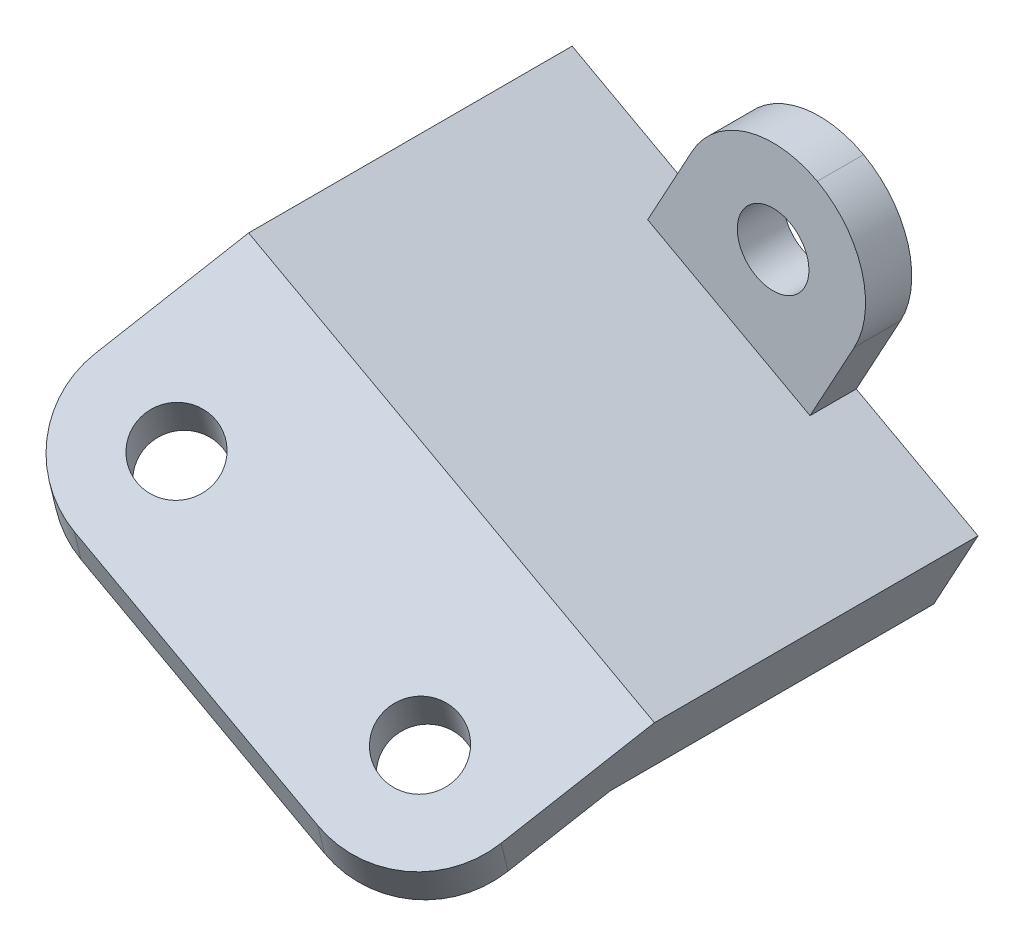
SolidWorks part; units mm, degrees
ref_plane "Front Plane" through (0, 0, 0) normal (0, 0, 1) x (1, 0, 0)
ref_plane "Top Plane" through (0, 0, 0) normal (0, 1, 0) x (1, 0, 0)
ref_plane "Right Plane" through (0, 0, 0) normal (1, 0, 0) x (0, 0, -1)
sketch "Sketch1" plane through (0, 0, 0) normal (0, 0, 1) x (1, 0, 0)
  line L0 (70, 136) -> (70, 0) construction
  line L2 (70, 114.8055) -> (60.4274, 97.2452)
  line L3 (60.4274, 97.2452) -> (53.4032, 101.0743)
  line L4 (53.4032, 101.0743) -> (62.9759, 118.6346)
  line L5 (62.9759, 118.6346) -> (70, 114.8055)
  dimension "D1" = 20
  dimension "D2" = 8
extrude "Boss-Extrude1" add sketch "Sketch1" along normal blind 2
fillet "Fillet1" radius 4 4 edges at (60.4274, 97.2452, 1) (53.4032, 101.0743, 1) (70, 114.8055, 1) (62.9759, 118.6346, 1)
sketch "Sketch2" plane through (0, 0, 2) normal (0, 0, 1) x (1, 0, 0)
  circle A0 centre (64.5734, 113.208) radius 1.55
  circle A1 centre (58.8298, 102.6718) radius 1.55
  dimension "D1" = 3.1
  dimension "D2" = 3.1
extrude "Cut-Extrude1" cut sketch "Sketch2" against normal up to next
sketch "Sketch3" plane through (0, 0, 2) normal (0, 0, 1) x (1, 0, 0)
  line L0 (66.1709, 107.7814) -> (59.1468, 111.6105)
  line L1 (62.3419, 100.7573) -> (68.0855, 111.2935) construction
  line L2 (61.0613, 115.1225) -> (55.3178, 104.5864) construction
  line L3 (64.2564, 104.2694) -> (57.2323, 108.0984)
  line L4 (65.2137, 106.0254) -> (58.1896, 109.8545) construction
  line L5 (66.1709, 107.7814) -> (71.439, 104.9096)
  line L6 (64.2564, 104.2694) -> (69.5245, 101.3976)
  line L7 (69.5245, 101.3976) -> (71.439, 104.9096)
  line L8 (59.1468, 111.6105) -> (53.8787, 114.4823)
  line L9 (53.8787, 114.4823) -> (51.9642, 110.9702)
  line L10 (51.9642, 110.9702) -> (57.2323, 108.0984)
  dimension "D3" = 6
  dimension "D1" = 2
  dimension "D2" = 2
  dimension "D4" = 6
extrude "Boss-Extrude2" add sketch "Sketch3" along normal blind 12 and the other way up to surface (2 mm away) other way up to face at (57.2798, 102.6718, 0)
sketch "Sketch4" plane through (-6.5751, 3.5843, 0) normal (-0.878, 0.4786, 0) x (0, 0, 1)
  line L0 (14, 122.3053) -> (20.9282, 118.3053)
  line L1 (14, 126.3053) -> (22.6603, 121.3053)
  line L2 (22.6603, 121.3053) -> (20.9282, 118.3053)
  line L3 (20.9282, 118.3053) -> (24.0467, 118.1828)
  line L4 (0, 122.3053) -> (14, 122.3053) construction
  line M4 (14, 122.3053) -> (14, 126.3053)
  dimension "D1" = 8
  dimension "D2" = 150
extrude "Boss-Extrude3" add sketch "Sketch4" against normal up to surface (20 mm away) contours L2 L1 L0 M4 region at (51.8756, 110.8076, 17.9132) up to face at (70.4818, 103.1536, 7)
fillet "Fillet2" radius 4 2 edges at (68.3279, 99.2025, 21.7942) (50.7676, 108.7752, 21.7942)
sketch "Sketch5" plane through (48.2419, 88.4962, 58.1918) normal (0.4145, 0.7604, 0.5) x (0.91, -0.3463, -0.2277)
  circle A0 centre (8.4754, 44.3609) radius 1.55
  circle A1 centre (20.053, 41.2052) radius 1.55
  dimension "D1" = 3.1
  dimension "D2" = 3.1
extrude "Cut-Extrude2" cut sketch "Sketch5" against normal up to next
